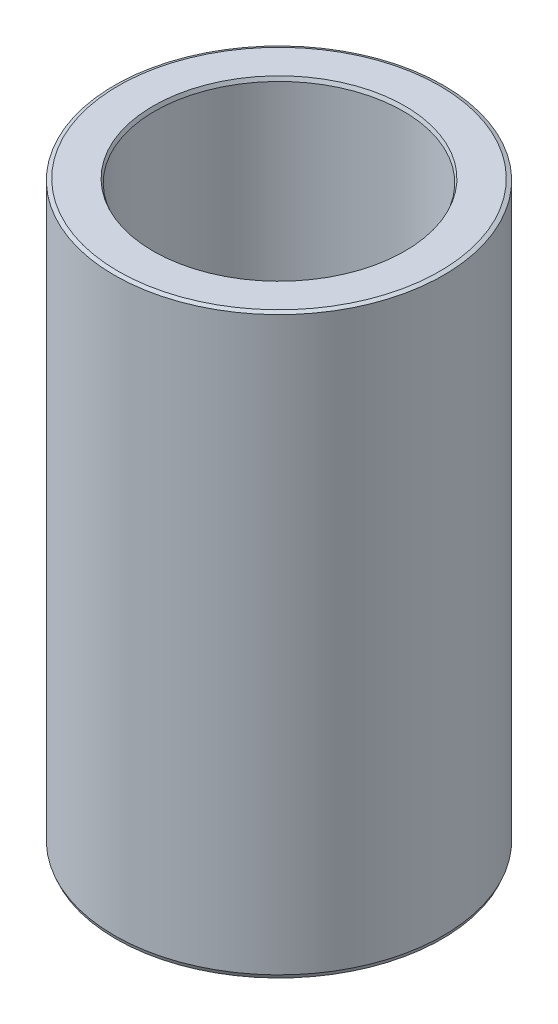
SolidWorks part; units mm, degrees
ref_plane "Front Plane" through (0, 0, 0) normal (0, 0, 1) x (1, 0, 0)
ref_plane "Top Plane" through (0, 0, 0) normal (0, 1, 0) x (1, 0, 0)
ref_plane "Right Plane" through (0, 0, 0) normal (1, 0, 0) x (0, 0, -1)
sketch "Sketch1" plane through (0, 0, 0) normal (0, 1, 0) x (1, 0, 0)
  circle A0 centre (0, 0) radius 30
  dimension "SLEEVE_OD" = 60
extrude "Boss-Extrude1" add sketch "Sketch1" along normal blind 105.2307
sketch "Sketch2" plane through (0, 0, 0) normal (0, 1, 0) x (1, 0, 0)
  circle A0 centre (0, 0) radius 22.6655
  dimension "BORE_D" = 45.331
extrude "Cut-Extrude1" cut sketch "Sketch2" along normal through all
chamfer "Chamfer1" distance 0.2785 angle 68.059 4 edges at (0, 105.2307, 22.6655) (0, 0, 22.6655) (0, 0, 30) (0, 105.2307, 30) first distance on face at (0, 105.2307, 22.6655) first distance on face at (0, 0, 22.6655) first distance on face at (0, 105.2307, 30)
